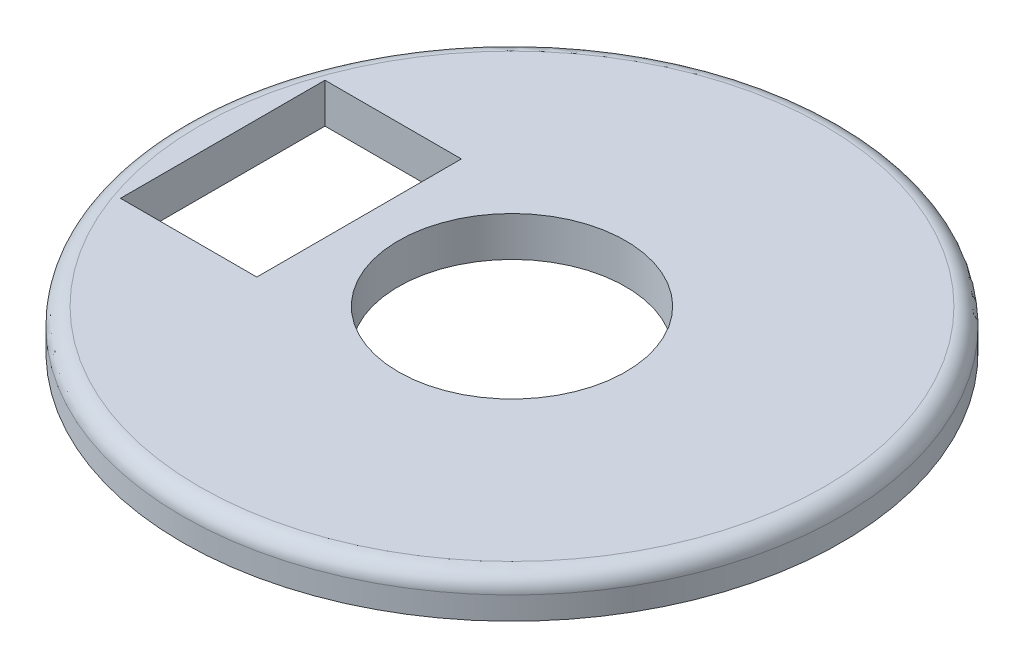
SolidWorks part; units mm, degrees
ref_plane "Front Plane" through (0, 0, 0) normal (0, 0, 1) x (1, 0, 0)
ref_plane "Top Plane" through (0, 0, 0) normal (0, 1, 0) x (1, 0, 0)
ref_plane "Right Plane" through (0, 0, 0) normal (1, 0, 0) x (0, 0, -1)
sketch "Sketch1" plane through (0, 0, 0) normal (0, 1, 0) x (1, 0, 0)
  circle A0 centre (0, 0) radius 184.15
  circle A1 centre (0, 0) radius 63.5
  dimension "D1" = 368.3
extrude "Boss-Extrude1" add sketch "Sketch1" along normal blind 22.225
fillet "Fillet1" radius 9.525 1 edges at (0, 22.225, 184.15)
sketch "Sketch2" plane through (0, 0, 0) normal (0, 1, 0) x (1, 0, 0)
  line L0 (0, 0) -> (-174.625, 0) construction
  line L2 (-85.4446, -57.15) -> (-161.6446, -57.15)
  line L3 (-85.4446, -57.15) -> (-85.4446, 57.15)
  line L4 (-85.4446, 57.15) -> (-161.6446, 57.15)
  line L5 (-161.6446, -57.15) -> (-161.6446, 57.15)
  line L6 (-85.4446, -57.15) -> (-161.6446, 57.15) construction
  line L7 (-85.4446, 57.15) -> (-161.6446, -57.15) construction
  circle A0 centre (0, 0) radius 174.625 construction
  circle A1 centre (0, 0) radius 174.625 construction
  circle A2 centre (0, 0) radius 171.45 construction
  point P6 (0, 0)
  point P12 (0, 0)
  point P13 (-130.6457, 0)
  point P14 (0, 0)
  point P15 (-130.6457, -0.5753)
  point P16 (0, 0)
  point P17 (-124.2389, 22.4695)
  point P18 (0, 0)
  point P21 (0, 0)
  point P22 (0, 0)
  point P23 (-161.1971, -58.4003)
  point P24 (-161.6052, 57.2613)
  dimension "D1" = 76.2
  dimension "D2" = 114.3
  dimension "D3" = 3.175
extrude "Cut-Extrude4" cut sketch "Sketch2" along normal through all
